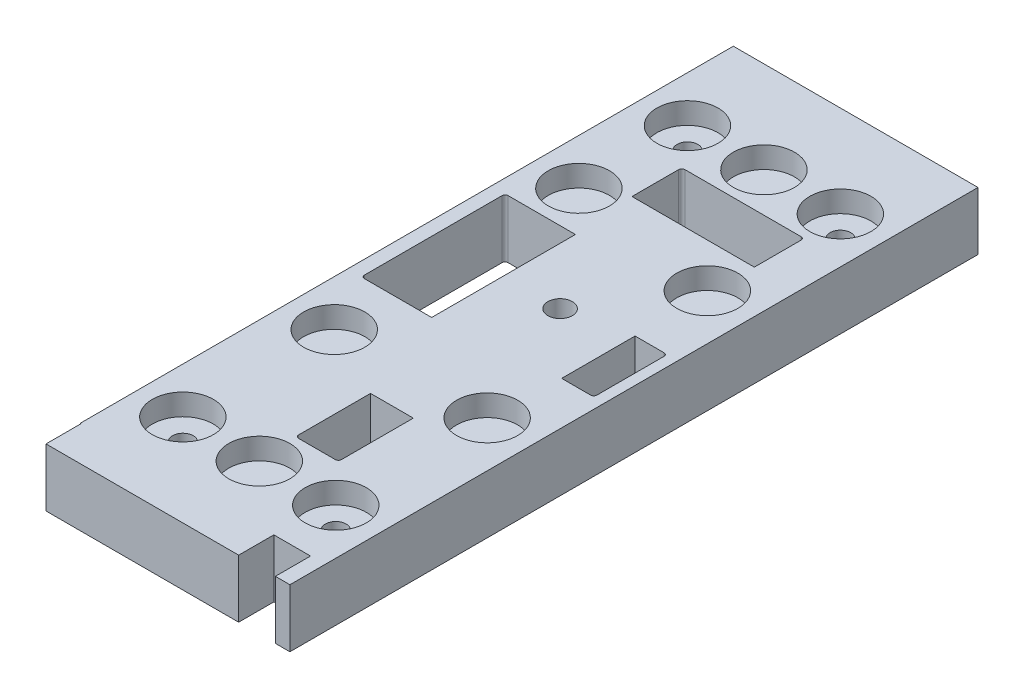
SolidWorks part; units mm, degrees
material "Plain Carbon Steel"
ref_plane "Front Plane" through (0, 0, 0) normal (0, 0, 1) x (1, 0, 0)
ref_plane "Top Plane" through (0, 0, 0) normal (0, 1, 0) x (1, 0, 0)
ref_plane "Right Plane" through (0, 0, 0) normal (1, 0, 0) x (0, 0, -1)
sketch "Sketch1" plane through (0, 0, 0) normal (0, 1, 0) x (1, 0, 0)
  line L1 (-40, -112.5) -> (40, -112.5)
  line L2 (-40, -112.5) -> (-40, 112.5)
  line L3 (-40, 112.5) -> (40, 112.5)
  line L4 (40, -112.5) -> (40, 112.5)
  line L5 (-40, -112.5) -> (40, 112.5) construction
  line L6 (-40, 112.5) -> (40, -112.5) construction
  point P0 (0, 0)
  dimension "D1" = 225
  dimension "D2" = 80
extrude "Boss-Extrude1" add sketch "Sketch1" against normal blind 19
sketch "Sketch2" plane through (0, 0, 0) normal (0, 1, 0) x (1, 0, 0)
  line L0 (-34.5, -13.64) -> (-12.5, -13.64) construction
  line L1 (-35.5, 32.36) -> (-35.5, -12.64) construction
  line L2 (-12.5, 33.36) -> (-34.5, 33.36) construction
  line L3 (-12.5, -13.64) -> (-12.5, 33.36) construction
  line L4 (0, -69.64) -> (12, -69.64) construction
  line L5 (-1, -45.14) -> (-1, -68.64) construction
  line L6 (13, -45.14) -> (-1, -45.14) construction
  line L7 (13, -68.64) -> (13, -45.14) construction
  line L8 (35.5, 14.36) -> (26, 14.36) construction
  line L9 (36.5, -8.64) -> (36.5, 13.36) construction
  line L10 (26, -9.64) -> (35.5, -9.64) construction
  line L11 (26, 14.36) -> (26, -9.64) construction
  line L12 (26, 53.36) -> (26, 68.64) construction
  line L13 (-14, 53.36) -> (26, 53.36) construction
  line L14 (-14, 68.64) -> (-14, 53.36) construction
  line L15 (25, 69.64) -> (-13, 69.64) construction
  line L16 (-34.5, -13.64) -> (-12.5, -13.64)
  line L17 (-35.5, 32.36) -> (-35.5, -12.64)
  line L18 (-12.5, 33.36) -> (-34.5, 33.36)
  line L19 (-12.5, -13.64) -> (-12.5, 33.36)
  line L20 (0, -69.64) -> (12, -69.64)
  line L21 (-1, -45.14) -> (-1, -68.64)
  line L22 (13, -45.14) -> (-1, -45.14)
  line L23 (13, -68.64) -> (13, -45.14)
  line L24 (35.5, 14.36) -> (26, 14.36)
  line L25 (36.5, -8.64) -> (36.5, 13.36)
  line L26 (26, -9.64) -> (35.5, -9.64)
  line L27 (26, 14.36) -> (26, -9.64)
  line L28 (26, 53.36) -> (26, 68.64)
  line L29 (-14, 53.36) -> (26, 53.36)
  line L30 (-14, 68.64) -> (-14, 53.36)
  line L31 (25, 69.64) -> (-13, 69.64)
  arc A0 (-35.5, -12.64) -> (-34.5, -13.64) centre (-34.5, -12.64) ccw construction
  arc A1 (-34.5, 33.36) -> (-35.5, 32.36) centre (-34.5, 32.36) ccw construction
  arc A2 (12, -69.64) -> (13, -68.64) centre (12, -68.64) ccw construction
  arc A3 (-1, -68.64) -> (0, -69.64) centre (0, -68.64) ccw construction
  arc A4 (36.5, 13.36) -> (35.5, 14.36) centre (35.5, 13.36) ccw construction
  arc A5 (35.5, -9.64) -> (36.5, -8.64) centre (35.5, -8.64) ccw construction
  arc A6 (26, 68.64) -> (25, 69.64) centre (25, 68.64) ccw construction
  arc A7 (-13, 69.64) -> (-14, 68.64) centre (-13, 68.64) ccw construction
  arc A8 (-35.5, -12.64) -> (-34.5, -13.64) centre (-34.5, -12.64) ccw
  arc A9 (-34.5, 33.36) -> (-35.5, 32.36) centre (-34.5, 32.36) ccw
  arc A10 (12, -69.64) -> (13, -68.64) centre (12, -68.64) ccw
  arc A11 (-1, -68.64) -> (0, -69.64) centre (0, -68.64) ccw
  arc A12 (36.5, 13.36) -> (35.5, 14.36) centre (35.5, 13.36) ccw
  arc A13 (35.5, -9.64) -> (36.5, -8.64) centre (35.5, -8.64) ccw
  arc A14 (26, 68.64) -> (25, 69.64) centre (25, 68.64) ccw
  arc A15 (-13, 69.64) -> (-14, 68.64) centre (-13, 68.64) ccw
extrude "Cut-Extrude1" cut sketch "Sketch2" against normal up to next
sketch "Sketch4" plane through (0, 0, 0) normal (0, 1, 0) x (1, 0, 0)
  circle A0 centre (25, -82.5) radius 10 construction
  circle A1 centre (0, -82.5) radius 10 construction
  circle A2 centre (-25, -82.5) radius 10 construction
  circle A3 centre (-25, -33) radius 10 construction
  circle A4 centre (25, -33) radius 10 construction
  circle A6 centre (25, 39) radius 10 construction
  circle A7 centre (-25, 47) radius 10 construction
  circle A8 centre (-25, 82.5) radius 10 construction
  circle A9 centre (0, 82.5) radius 10 construction
  circle A10 centre (25, 82.5) radius 10 construction
  circle A11 centre (25, -82.5) radius 10
  circle A12 centre (0, -82.5) radius 10
  circle A13 centre (-25, -82.5) radius 10
  circle A14 centre (-25, -33) radius 10
  circle A15 centre (25, -33) radius 10
  circle A17 centre (25, 39) radius 10
  circle A18 centre (-25, 47) radius 10
  circle A19 centre (-25, 82.5) radius 10
  circle A20 centre (0, 82.5) radius 10
  circle A21 centre (25, 82.5) radius 10
extrude "Cut-Extrude2" cut sketch "Sketch4" against normal blind 7
sketch "Sketch5" plane through (0, -19, 0) normal (0, -1, 0) x (1, 0, 0)
  circle A0 centre (6, 100) radius 8.5
  circle A1 centre (6, -100) radius 8.5
  dimension "D1" = 17
extrude "Cut-Extrude3" cut sketch "Sketch5" against normal blind 5
sketch "Sketch7" plane through (0, 0, 0) normal (0, 1, 0) x (1, 0, 0)
  line L0 (-40, -112.5) -> (40, -112.5) construction
  line L1 (23.25, -112.5) -> (35.25, -112.5)
  line L2 (23.25, -112.5) -> (23.25, -101)
  line L3 (23.25, -101) -> (35.25, -101)
  line L4 (35.25, -112.5) -> (35.25, -101)
  line L5 (24.25, -115) -> (24.25, -102.5) construction
  line L6 (34.25, -102.5) -> (34.25, -115) construction
  line L7 (24.75, -102) -> (33.75, -102) construction
  line L8 (-50.25, -102) -> (-41.25, -102) construction
  line L9 (-39.75, -112.5) -> (-40.75, -112.5)
  line L10 (-39.75, -112.5) -> (-39.75, -101)
  line L11 (-39.75, -101) -> (-40.75, -101)
  line L12 (-40.75, -112.5) -> (-40.75, -101)
  line L13 (-40.75, -102.5) -> (-40.75, -115) construction
  dimension "D1" = 1
  dimension "D2" = 1
  dimension "D3" = 1
  dimension "D4" = 1
  dimension "D5" = 1
  dimension "D6" = 1
extrude "Cut-Extrude4" cut sketch "Sketch7" against normal up to next
hole_wizard "M8 Tapped Hole1" positions "Sketch10" profile "Sketch9" tap size "M8" standard "ISO" end condition through all
sketch "Sketch10" plane through (0, 0, 0) normal (0, 1, 0) x (1, 0, 0)
  point P0 (-25, 82.5)
  point P3 (25, 82.5)
  point P6 (25, -82.5)
  point P9 (-25, -82.5)
sketch "Sketch9" plane through (-25, 0, -82.5) normal (1, 0, 0) x (0, 0, 1)
  line L0 (0, 0) -> (0, 19)
  line L1 (0, 19) -> (3.4, 19)
  line L2 (3.4, 19) -> (3.4, 0)
  line L5 (3.4, 0) -> (0, 0)
  line L11 (0, -6.35) -> (0, 107.95) construction
  dimension "Thru Tap Drill Dia." = 6.8
  dimension "Thru Tap Drill Depth" = 19
cosmetic thread "Hole Thread1" parameters "D2"=8
cosmetic thread "Hole Thread2" parameters "D2"=8
cosmetic thread "Hole Thread3" parameters "D2"=8
cosmetic thread "Hole Thread4" parameters "D2"=8
sketch "Sketch11" plane through (0, 0, 0) normal (0, 1, 0) x (1, 0, 0)
  circle A0 centre (6, 9.86) radius 4
  dimension "D1" = 8
extrude "Cut-Extrude5" cut sketch "Sketch11" against normal through all
